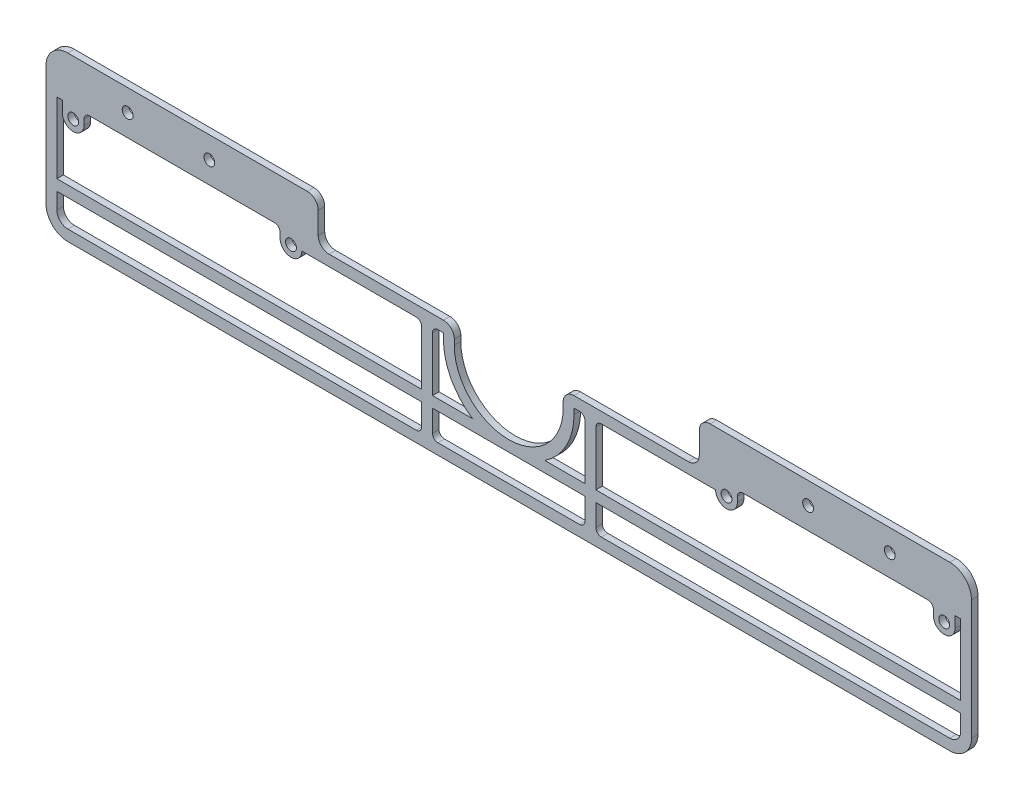
SolidWorks part; units mm, degrees
ref_plane "Front Plane" through (0, 0, 0) normal (0, 0, 1) x (1, 0, 0)
ref_plane "Top Plane" through (0, 0, 0) normal (0, 1, 0) x (1, 0, 0)
ref_plane "Right Plane" through (0, 0, 0) normal (1, 0, 0) x (0, 0, -1)
sketch "Sketch1" plane through (0, 0, 0) normal (0, 0, 1) x (1, 0, 0)
  line L0 (-50, 0) -> (-50, 35) construction
  line L1 (405, -95) -> (-405, -95) construction
  line L4 (-425, -75) -> (-425, 35)
  line L8 (-60, 55) -> (-405, 55) construction
  line L21 (-165.0003, 15) -> (-60, 15)
  line L25 (0, -50) -> (0, -95)
  line L26 (0, 55) -> (0, -95) construction
  line L27 (-50, 75) -> (50, 75) construction
  line L32 (-50, 5) -> (-50, 0)
  line L34 (0, -95) -> (-405, -95)
  line L170 (-405, 55) -> (-185.0003, 55)
  line L175 (-175.0003, 45) -> (-175.0003, 25)
  circle A1 centre (0, 0) radius 30 construction
  arc A4 (-405, -95) -> (-425, -75) centre (-405, -75) cw
  arc A5 (-425, 35) -> (-405, 55) centre (-405, 35) cw
  circle A26 centre (-350, 35) radius 5
  circle A27 centre (-275, 35) radius 5
  arc A136 (-50, 0) -> (0, -50) centre (0, 0) ccw
  arc A137 (-50, 5) -> (-60, 15) centre (-60, 5) ccw
  arc A138 (-165.0003, 15) -> (-175.0003, 25) centre (-165.0003, 25) cw
  arc A139 (-175.0003, 45) -> (-185.0003, 55) centre (-185.0003, 45) ccw
  point P11 (0, 30)
  point P15 (-50, 15)
  point P27 (-175.0003, 55)
  point P30 (-50, 55)
  point P74 (0, 75)
  dimension "D3" = 10
  dimension "D4" = 60
  dimension "D6" = 55
  dimension "D7" = 425
  dimension "D10" = 175.0003
  dimension "D11" = 20
  dimension "D12" = 50
  dimension "D20" = 10
  dimension "D21" = 10
  dimension "D5" = 150
  dimension "D9" = 40
  dimension "D16" = 100
  dimension "D17" = 20
  dimension "D18" = 375
  dimension "D19" = 20
  dimension "D22" = 20
  dimension "D23" = 75
  dimension "D24" = 225
  dimension "D8" = 345
extrude "Boss-Extrude1" add sketch "Sketch1" along normal blind 6
mirror "Mirror1" about plane through (0, -50, 6) normal (-1, 0, 0) of "Boss-Extrude1"
sketch "Sketch2" plane through (0, 0, 6) normal (0, 0, 1) x (1, 0, 0)
  line L0 (0, -29.253) -> (0, -89.121) construction
  line L2 (-185.0003, 55) -> (-405, 55) construction
  line L49 (-410, 5) -> (-410, 15)
  line L50 (-410, 15) -> (-415, 15)
  line L51 (-390, 5) -> (-390, 10)
  line L52 (-385, 15) -> (-215, 15)
  line L53 (-210, 10) -> (-210, 5)
  line L54 (-190, 5) -> (-165.0003, 5)
  line L55 (-185.0003, 45) -> (-405, 45)
  line L56 (-185.0003, 25) -> (-185.0003, 45)
  line L57 (-60, 0) -> (-60, 5)
  line L58 (-60, 5) -> (-165.0003, 5)
  line L59 (-415, 35) -> (-415, -75)
  line L60 (-405, -85) -> (405, -85)
  line L61 (-185.0003, 45) -> (-405, 45) construction
  line L62 (-185.0003, 25) -> (-185.0003, 45) construction
  line L63 (-60, 0) -> (-60, 5)
  line L64 (-85, 5) -> (-165.0003, 5)
  line L65 (-415, 35) -> (-415, -75) construction
  line L66 (-405, -85) -> (-85, -85)
  line L67 (0, -60) -> (0, -85)
  line L68 (-415, 15) -> (-415, -75)
  line L69 (-80, 0) -> (-80, -80)
  line L70 (-70, 0) -> (-70, -80)
  line L71 (-65, 5) -> (-60, 5)
  line L72 (-65, -85) -> (0, -85)
  circle A0 centre (-400, 5) radius 5
  circle A1 centre (-200, 5) radius 5
  arc A2 (-410, 5) -> (-390, 5) centre (-400, 5) ccw
  arc A3 (-210, 5) -> (-190, 5) centre (-200, 5) ccw
  arc A4 (-65, -85) -> (-70, -80) centre (-65, -80) cw
  arc A5 (-70, 0) -> (-65, 5) centre (-65, 0) cw
  arc A43 (-80, 0) -> (-85, 5) centre (-85, 0) ccw
  arc A44 (-85, -85) -> (-80, -80) centre (-85, -80) ccw
  arc A45 (-385, 15) -> (-390, 10) centre (-385, 10) ccw
  arc A46 (-210, 10) -> (-215, 15) centre (-215, 10) ccw
  arc A49 (-405, 45) -> (-415, 35) centre (-405, 35) ccw
  arc A50 (-185.0003, 25) -> (-165.0003, 5) centre (-165.0003, 25) ccw
  arc A51 (-60, 0) -> (60, 0) centre (0, 0) ccw
  arc A52 (-415, -75) -> (-405, -85) centre (-405, -75) ccw
  arc A53 (-405, 45) -> (-415, 35) centre (-405, 35) ccw construction
  arc A54 (-185.0003, 25) -> (-165.0003, 5) centre (-165.0003, 25) ccw construction
  arc A55 (-60, 0) -> (0, -60) centre (0, 0) ccw
  arc A56 (-415, -75) -> (-405, -85) centre (-405, -75) ccw
  point P8 (-400, 15)
  point P34 (-70, -85)
  point P37 (-70, 5)
  dimension "D1" = 10
  dimension "D3" = 20
  dimension "D9" = 5
  dimension "D10" = 5
  dimension "D11" = 5
  dimension "D12" = 5
  dimension "D2" = 40
  dimension "D4" = 400
  dimension "D5" = 200
  dimension "D7" = 20
  dimension "D8" = 10
  dimension "D6" = 10
extrude "Cut-Extrude1" cut sketch "Sketch2" against normal through all contours L68 A56 L66 L67 A55 L63 L64 L54 A3 L53 L52 L51 A2 L49 L50 | A1 | A0 | A55 L63 L71 A5 L70 A4 L72 L67 | A55 L67 L72 A4 L70 A5 L71 L63 region at (-250.1525, -37.4707, 6) region at (-43.8862, -57.0304, 6) region at (-400, 5, 6) region at (-200, 5, 6)
mirror "Mirror2" about plane through (0, 0, 0) normal (1, 0, 0) of "Cut-Extrude1"
sketch "Sketch5" plane through (0, 0, 6) normal (0, 0, 1) x (1, 0, 0)
  line L0 (-425, -50) -> (425, -50)
  line L1 (-425, 35) -> (-425, -75) construction
  line L2 (425, 35) -> (425, -75) construction
  line L3 (425, -50) -> (425, -60)
  line L4 (425, -60) -> (-425, -60)
  line L5 (-425, -60) -> (-425, -50)
  arc A0 (-50, 0) -> (50, 0) centre (0, 0) ccw construction
  arc A1 (-60, 0) -> (60, 0) centre (0, 0) ccw construction
extrude "Boss-Extrude3" add sketch "Sketch5" against normal up to surface (6 mm away) up to face at (0, -30.8333, 0)
